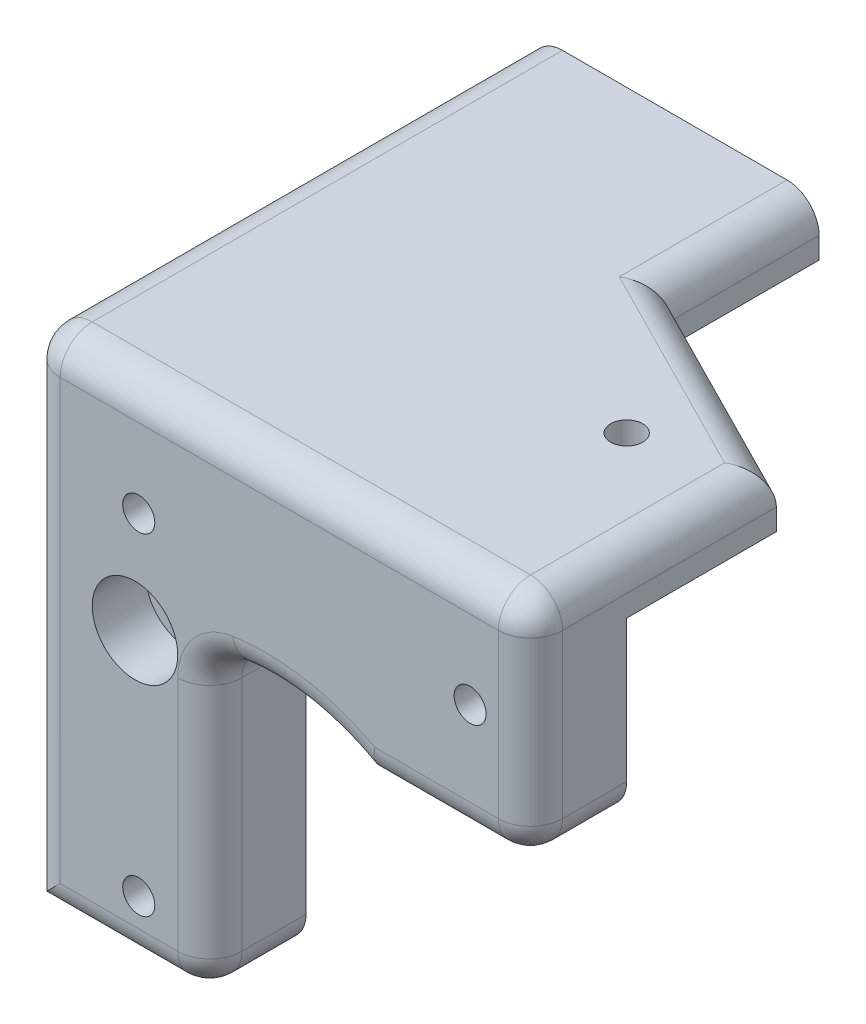
SolidWorks part; units mm, degrees
ref_plane "Front Plane" through (0, 0, 0) normal (0, 0, 1) x (1, 0, 0)
ref_plane "Top Plane" through (0, 0, 0) normal (0, 1, 0) x (1, 0, 0)
ref_plane "Right Plane" through (0, 0, 0) normal (1, 0, 0) x (0, 0, -1)
sketch "Sketch2" plane through (0, 0, 0) normal (0, 0, 1) x (1, 0, 0)
  line L0 (0, 0) -> (0, 47)
  line L1 (0, 47) -> (47, 47)
  line L2 (47, 47) -> (47, 25.75)
  line L3 (47, 25.75) -> (31.68, 25.75)
  line L4 (17, 0) -> (17, 27.58)
  line L5 (17, 0) -> (0, 0)
  arc A0 (17, 27.58) -> (31.68, 25.75) centre (22.2111, 9.5871) cw
  dimension "D1" = 47
  dimension "D2" = 47
  dimension "D3" = 21.25
  dimension "D4" = 17
  dimension "D5" = 27.58
  dimension "D6" = 15.32
extrude "Boss-Extrude1" add sketch "Sketch2" along normal blind 9
sketch "Sketch3" plane through (0, 0, 9) normal (0, 0, 1) x (1, 0, 0)
  line L0 (0, 0) -> (17, 0) construction
  line L1 (0, 47) -> (0, 0) construction
  line L3 (47, 47) -> (0, 47) construction
  circle A0 centre (10.35, 5.65) radius 1.5
  circle A1 centre (10.35, 36.65) radius 1.5
  circle A2 centre (41.35, 36.65) radius 1.5
  dimension "D1" = 3
  dimension "D5" = 3
  dimension "D6" = 3
  dimension "D2" = 5.65
  dimension "D3" = 10.35
  dimension "D4" = 31
  dimension "D7" = 10.35
  dimension "D8" = 31
extrude "Cut-Extrude1" cut sketch "Sketch3" against normal blind 10
sketch "Sketch8" plane through (0, 0, 0) normal (0, 0, -1) x (-1, 0, 0)
  line L0 (0, 0) -> (-17, 0) construction
  line L1 (0, 47) -> (-5, 47)
  line L2 (0, 47) -> (0, 0)
  line L3 (0, 0) -> (-5, 0)
  line L4 (-5, 47) -> (-5, 0)
  dimension "D1" = 5
extrude "Boss-Extrude2" add sketch "Sketch8" along normal blind 38
sketch "Sketch9" plane through (0, 0, 0) normal (0, 0, -1) x (-1, 0, 0)
  line L0 (-47, 25.75) -> (-47, 47) construction
  line L1 (-5, 47) -> (-47, 47)
  line L2 (-5, 47) -> (-5, 42)
  line L3 (-5, 42) -> (-47, 42)
  line L4 (-47, 47) -> (-47, 42)
  dimension "D1" = 5
extrude "Boss-Extrude3" add sketch "Sketch9" along normal blind 38
sketch "Sketch10" plane through (0, 0, 0) normal (-1, 0, 0) x (0, 0, 1)
  line L0 (0, 0) -> (-23, 32)
  line L1 (-23, 32) -> (-38, 32)
  line L2 (-38, 0) -> (-38, 47) construction
  line L3 (-38, 32) -> (-38, 0)
  line L4 (-38, 0) -> (0, 0)
  dimension "D1" = 15
  dimension "D2" = 15
extrude "Cut-Extrude2" cut sketch "Sketch10" against normal blind 38
sketch "Sketch11" plane through (0, 0, 9) normal (0, 0, 1) x (1, 0, 0)
  line L0 (0, 47) -> (0, 0) construction
  line L1 (47, 47) -> (0, 47) construction
  circle A0 centre (10, 27) radius 4
  dimension "D1" = 8
  dimension "D2" = 10
  dimension "D3" = 20
extrude "Cut-Extrude3" cut sketch "Sketch11" against normal blind 5
sketch "Sketch12" plane through (0, 42, 0) normal (0, -1, 0) x (1, 0, 0)
  line L0 (47, -38) -> (47, -14)
  line L1 (47, -38) -> (47, 0) construction
  line L2 (47, -14) -> (27, -24.1488)
  line L3 (27, -24.1488) -> (27, -38)
  line L4 (47, -38) -> (5, -38) construction
  line L5 (27, -38) -> (47, -38)
  dimension "D1" = 14
  dimension "D2" = 20
extrude "Cut-Extrude4" cut sketch "Sketch12" against normal blind 10
sketch "Sketch13" plane through (0, 42, 0) normal (0, -1, 0) x (1, 0, 0)
  line L0 (47, -14) -> (47, 0) construction
  line L1 (47, 0) -> (5, 0) construction
  circle A0 centre (37, -10) radius 1.5
  dimension "D1" = 3
  dimension "D2" = 10
  dimension "D3" = 10
extrude "Cut-Extrude5" cut sketch "Sketch13" against normal through all
sketch "Sketch14" plane through (0, 42, 0) normal (0, -1, 0) x (-1, 0, 0)
  circle A0 centre (-37, 10) radius 3
  dimension "D1" = 6
extrude "Cut-Extrude6" cut sketch "Sketch14" against normal blind 2
fillet "Fillet1" radius 3 16 edges at (47, 25.75, 4.5) (17, 0, 4.5) (8.5, 0, 9) (17, 27.58, 4.5) (39.34, 25.75, 9) (24.5283, 28.1755, 9) (17, 13.79, 9) (47, 36.375, 9) (47, 47, -2.5) (37, 47, -19.0744) (27, 47, -31.0744) (0, 32, -30.5) (0, 16, -11.5) (0, 23.5, 9) (23.5, 47, 9) (0, 47, -14.5)
